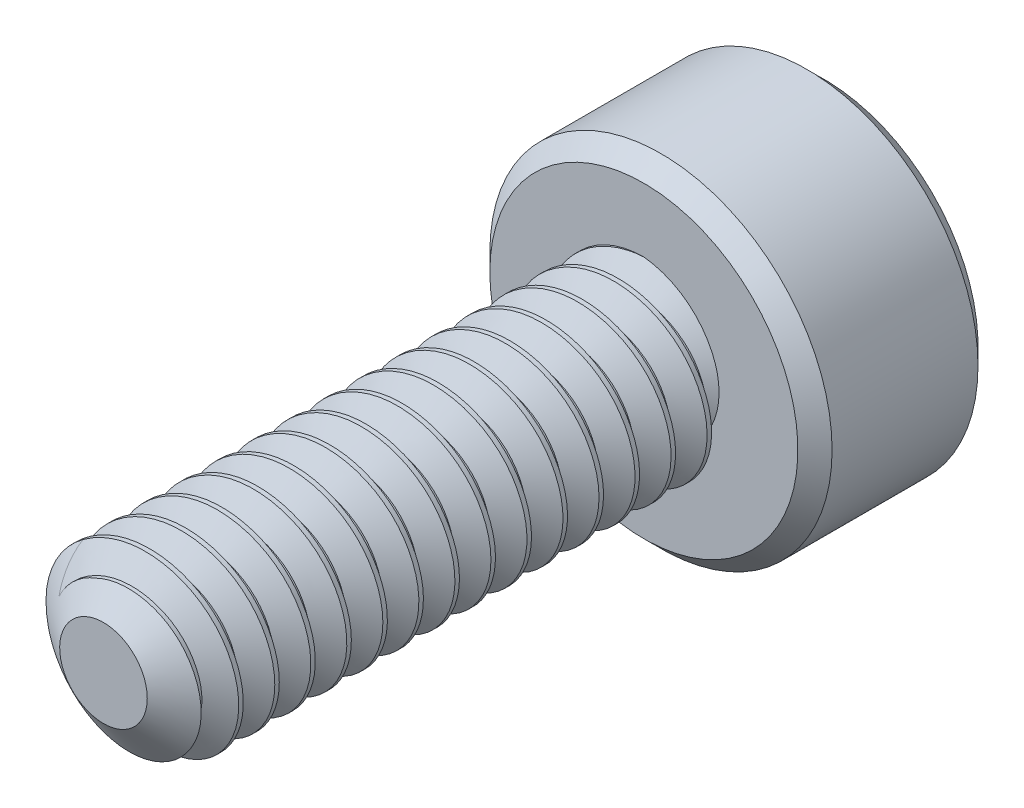
SolidWorks part; units mm, degrees
ref_plane "Front Plane" through (0, 0, 0) normal (0, 0, 1) x (1, 0, 0)
ref_plane "Top Plane" through (0, 0, 0) normal (0, 1, 0) x (1, 0, 0)
ref_plane "Right Plane" through (0, 0, 0) normal (1, 0, 0) x (0, 0, -1)
sketch "Sketch1" plane through (0, 0, 0) normal (0, 0, 1) x (1, 0, 0)
  circle A0 centre (0, 0) radius 1
  dimension "OD" = 2
extrude "Extrude1" add sketch "Sketch1" against normal blind 6
sketch "Sketch2" plane through (0, 0, 0) normal (0, 0, 1) x (1, 0, 0)
  circle A0 centre (0, 0) radius 1 construction
  circle A1 centre (0, 0) radius 1
curve "Helix/Spiral1" pitch 0.4 height 6.4 radius 1 centre (0, 0, 0) axis (0, 0, -1) start towards (0, 1, 0) parameters "pitch"=0.4
sketch "Sketch3" plane through (0, 0, 0) normal (1, 0, 0) x (0, 0, -1)
  line L0 (-0.35, 1) -> (-0.2, 0.7402)
  line L1 (-0.2, 0.7402) -> (-0.15, 0.7402)
  line L2 (-0.15, 0.7402) -> (0, 1)
  line L3 (-0.35, 1) -> (0, 1)
  line L4 (-0.175, 1) -> (-0.175, 0.7402) construction
  line L5 (-0.275, 0.8701) -> (-0.075, 0.8701) construction
  line L6 (0, 1) -> (0, -1) construction
  dimension "D1" = 0.05
  dimension "D2" = 0.2
  dimension "D3" = 60
sweep "Cut-Sweep1" cut profiles "Sketch3" path "Helix/Spiral1" align with end faces yes
sketch "Sketch4" plane through (0, 0, 0) normal (1, 0, 0) x (0, 0, -1)
  line L0 (0.3598, 1) -> (0, 0.4862)
  line L1 (0, 0.4862) -> (0, 1)
  line L2 (0.3598, 1) -> (0, 1)
  line L3 (-0.35, 1) -> (0, 1) construction
  line L4 (0, 0) -> (7.0209, 0) construction
  dimension "D1" = 55
  dimension "D2" = 0.254
revolve "Cut-Revolve1" cut sketch "Sketch4" angle 360 about L4
sketch "Sketch6" plane through (0, 0, -6) normal (0, 0, -1) x (-1, 0, 0)
  circle A0 centre (0, 0) radius 1.9
  dimension "head dia" = 3.8
extrude "Extrude2" add sketch "Sketch6" along normal blind 2
sketch "Sketch7" plane through (0, 0, -8) normal (0, 0, -1) x (-1, 0, 0)
  line L1 (0, 0.866) -> (-0.75, 0.433)
  line L2 (-0.75, 0.433) -> (-0.75, -0.433)
  line L3 (-0.75, -0.433) -> (0, -0.866)
  line L4 (0, -0.866) -> (0.75, -0.433)
  line L5 (0.75, -0.433) -> (0.75, 0.433)
  line L6 (0.75, 0.433) -> (0, 0.866)
  circle A0 centre (0, 0) radius 0.75 construction
  dimension "hex dia" = 1.5
extrude "Cut-Extrude1" cut sketch "Sketch7" against normal blind 1.125
sketch "Sketch8" plane through (0, 0, -8) normal (0, 0, -1) x (-1, 0, 0)
  circle A0 centre (0, 0) radius 0.866
extrude "Cut-Extrude2" cut sketch "Sketch8" against normal through all draft 45
chamfer "Chamfer1" distance 0.19 angle 45 2 edges at (-1.9, 0, -8) (-1.9, 0, -6)
sketch "Sketch10" plane through (0, 0, -6) normal (0, 0, 1) x (1, 0, 0)
  circle A1 centre (0, 0) radius 1
  circle A2 centre (0, 0) radius 1
  dimension "D1" = 0
ref_plane "Plane1" through (0, 0, 0) normal (0, 0, 1) x (1, 0, 0)
extrude "partial thread" [suppressed] add sketch "Sketch10" along normal up to surface (2 mm away) separate body up to plane "Plane1"
chamfer "Chamfer2" [suppressed] distance 0.04 angle 45
combine bodies "Combine1" [suppressed] operation type add bodies to combine 107 108
sketch "Sketch9" plane through (0, 0, 0) normal (1, 0, 0) x (0, 0, -1)
  line L0 (0, 1) -> (0, -1) construction
  line L1 (1, 1) -> (1, -1) construction
  dimension "D1" = 1
equation "\"D3@Helix/Spiral1\" = \"screw length@Extrude1\"+\"pitch@Helix/Spiral1\""
equation "\"D1@Sketch3\" = \"pitch@Helix/Spiral1\"*.125"
equation "\"D2@Sketch3\" = \"pitch@Helix/Spiral1\"*.5"
equation "\"D1@Cut-Extrude1\" = \"hex dia@Sketch7\"*.75"
equation "\"D1@Chamfer1\" = \"head dia@Sketch6\"*.05"
equation "\"D1@Sketch9\" = \"pitch@Helix/Spiral1\"*2.5"
equation "\"D1@Chamfer2\"=\"OD@Sketch1\"*.02"
